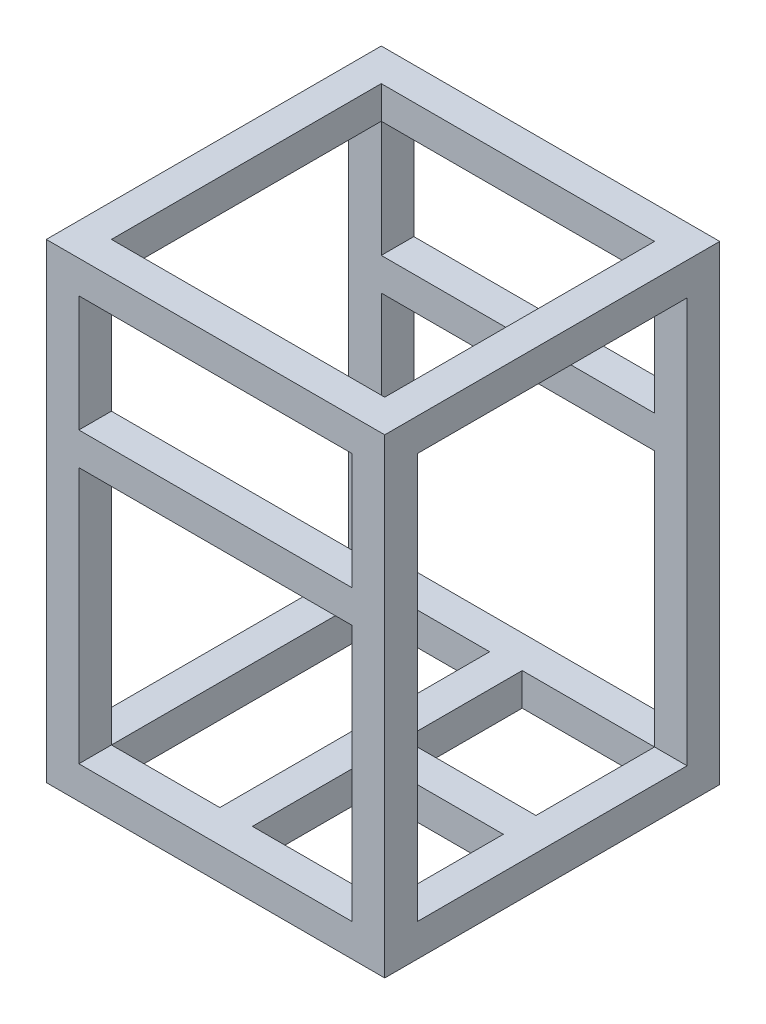
SolidWorks part; units mm, degrees
ref_plane "Front" through (0, 0, 0) normal (0, 0, 1) x (1, 0, 0)
ref_plane "Top" through (0, 0, 0) normal (0, 1, 0) x (1, 0, 0)
ref_plane "Right" through (0, 0, 0) normal (1, 0, 0) x (0, 0, -1)
sketch "Croquis1" plane through (0, 0, 0) normal (0, 1, 0) x (1, 0, 0)
  line L0 (131.9512, 65.3) -> (54.9512, 65.3) construction
  line L1 (0, 0) -> (131.9512, 0)
  line L2 (0, 0) -> (0, 130.6)
  line L3 (0, 130.6) -> (131.9512, 130.6)
  line L4 (131.9512, 0) -> (131.9512, 130.6)
  line L5 (12.7, 12.7) -> (54.9512, 12.7)
  line L6 (12.7, 12.7) -> (12.7, 117.9)
  line L7 (12.7, 117.9) -> (54.9512, 117.9)
  line L8 (119.2512, 12.7) -> (119.2512, 58.95)
  line L9 (54.9512, 65.3) -> (61.3012, 65.3) construction
  line L10 (54.9512, 12.7) -> (54.9512, 117.9)
  line L12 (67.6512, 117.9) -> (119.2512, 117.9)
  line L13 (67.6512, 12.7) -> (119.2512, 12.7)
  line L14 (119.2512, 71.65) -> (67.6512, 71.65)
  line L15 (119.2512, 58.95) -> (67.6512, 58.95)
  line L16 (119.2512, 71.65) -> (119.2512, 117.9)
  line L17 (67.6512, 12.7) -> (67.6512, 58.95)
  line L18 (67.6512, 71.65) -> (67.6512, 117.9)
  dimension "D1" = 105.2
  dimension "D2" = 12.7
  dimension "D3" = 12.7
  dimension "D4" = 12.7
  dimension "D5" = 12.7
  dimension "D6" = 77
  dimension "D7" = 6.35
  dimension "D10" = 6.35
  dimension "D9" = 12.7
extrude "Saliente-Extruir1" add sketch "Croquis1" along normal blind 12.7
sketch "Croquis2" plane through (0, 12.7, 0) normal (0, 1, 0) x (1, 0, 0)
  line L1 (12.7, 117.9) -> (0, 117.9)
  line L2 (12.7, 117.9) -> (12.7, 130.6)
  line L3 (12.7, 130.6) -> (0, 130.6)
  line L4 (0, 117.9) -> (0, 130.6)
  line L5 (12.7, 12.7) -> (0, 12.7)
  line L6 (12.7, 12.7) -> (12.7, 0)
  line L7 (12.7, 0) -> (0, 0)
  line L8 (0, 12.7) -> (0, 0)
  line L9 (119.2512, 117.9) -> (131.9512, 117.9)
  line L10 (119.2512, 117.9) -> (119.2512, 130.6)
  line L11 (119.2512, 130.6) -> (131.9512, 130.6)
  line L12 (131.9512, 117.9) -> (131.9512, 130.6)
  line L13 (119.2512, 12.7) -> (131.9512, 12.7)
  line L14 (119.2512, 12.7) -> (119.2512, 0)
  line L15 (119.2512, 0) -> (131.9512, 0)
  line L16 (131.9512, 12.7) -> (131.9512, 0)
extrude "Saliente-Extruir2" add sketch "Croquis2" along normal blind 158
sketch "Croquis3" plane through (0, 170.7, 0) normal (0, 1, 0) x (1, 0, 0)
  line L1 (0, 0) -> (131.9512, 0)
  line L2 (0, 0) -> (0, 130.6)
  line L3 (0, 130.6) -> (131.9512, 130.6)
  line L4 (131.9512, 0) -> (131.9512, 130.6)
  line L20 (12.7, 12.7) -> (119.2512, 12.7)
  line L21 (12.7, 12.7) -> (12.7, 117.9)
  line L22 (12.7, 117.9) -> (119.2512, 117.9)
  line L23 (119.2512, 12.7) -> (119.2512, 117.9)
  line M1 (12.7, 0) -> (12.7, 12.7)
  line M2 (12.7, 12.7) -> (0, 12.7)
  line M3 (0, 12.7) -> (0, 0)
  line M4 (0, 0) -> (12.7, 0)
extrude "Saliente-Extruir3" add sketch "Croquis3" along normal blind 12.7 contours L1 L4 L3 L2 L21 | M4 M1 M2 M3 region at (6.35, 170.7, -6.35) region at (14.5565, 170.7, -6.35)
sketch "Croquis4" plane through (119.2512, 0, 0) normal (-1, 0, 0) x (0, 0, 1)
  line L0 (0, 170.7) -> (0, 12.7) construction
  line L1 (0, 125.4) -> (-12.7, 125.4)
  line L2 (0, 125.4) -> (0, 112.7)
  line L3 (0, 112.7) -> (-12.7, 112.7)
  line L4 (-12.7, 125.4) -> (-12.7, 112.7)
  line L5 (-12.7, 170.7) -> (-12.7, 12.7) construction
  line L6 (-12.7, 12.7) -> (0, 12.7) construction
  line L7 (-65.3, 0) -> (-65.3, 170.7) construction
  line L8 (-130.6, 0) -> (0, 0) construction
  line L9 (-12.7, 170.7) -> (-117.9, 170.7) construction
  line L10 (-117.9, 125.4) -> (-117.9, 112.7)
  line L11 (-130.6, 112.7) -> (-117.9, 112.7)
  line L12 (-130.6, 125.4) -> (-130.6, 112.7)
  line L13 (-130.6, 125.4) -> (-117.9, 125.4)
  dimension "D1" = 100
  dimension "D2" = 12.7
extrude "Saliente-Extruir4" add sketch "Croquis4" along normal up to next
